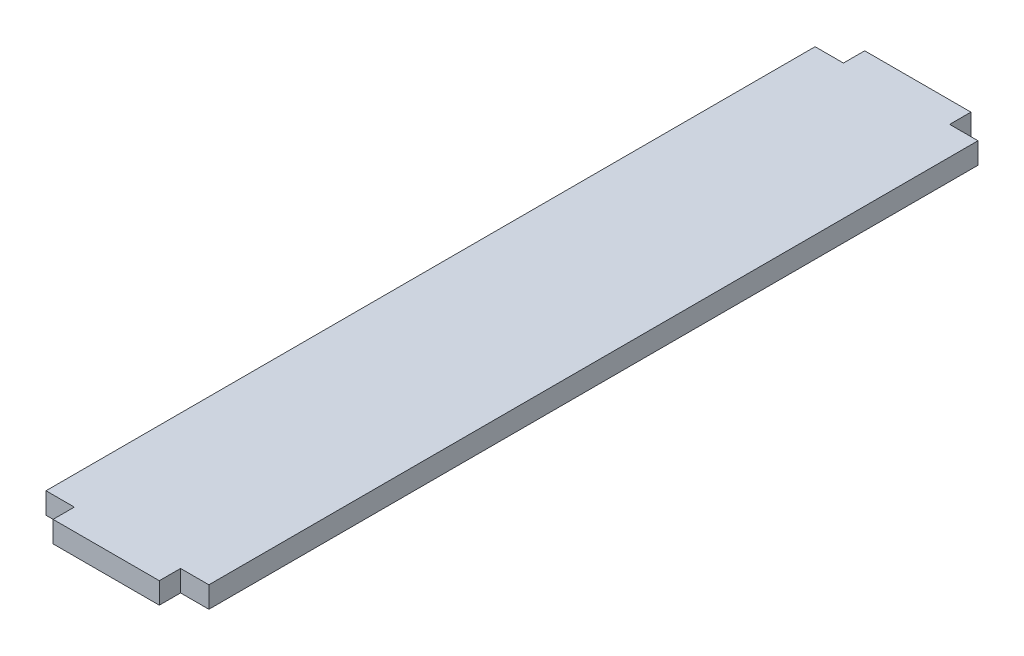
SolidWorks part; units mm, degrees
material "AISI 304"
ref_plane "Front Plane" through (0, 0, 0) normal (0, 0, 1) x (1, 0, 0)
ref_plane "Top Plane" through (0, 0, 0) normal (0, 1, 0) x (1, 0, 0)
ref_plane "Right Plane" through (0, 0, 0) normal (1, 0, 0) x (0, 0, -1)
sketch "Sketch1" plane through (0, 0, 0) normal (0, 1, 0) x (1, 0, 0)
  line L0 (3.75, 27.15) -> (5.75, 27.15)
  line L1 (-5.75, -27.15) -> (-3.75, -27.15)
  line L2 (-5.75, -27.15) -> (-5.75, -19.45)
  line L3 (-5.75, 27.15) -> (-3.75, 27.15)
  line L4 (5.75, -27.15) -> (5.75, -14.45)
  line L5 (-5.75, -27.15) -> (5.75, 27.15) construction
  line L6 (-5.75, 27.15) -> (5.75, -27.15) construction
  line L8 (3.75, 27.15) -> (3.75, 28.65)
  line L9 (3.75, 28.65) -> (-3.75, 28.65)
  line L10 (-3.75, 27.15) -> (-3.75, 28.65)
  line L12 (-3.75, -27.15) -> (-3.75, -28.65)
  line L13 (-3.75, -28.65) -> (3.75, -28.65)
  line L14 (3.75, -27.15) -> (3.75, -28.65)
  line L15 (3.75, -27.15) -> (5.75, -27.15)
  line L16 (-5.75, -17.75) -> (-5.75, 27.15)
  line L21 (5.75, -12.75) -> (5.75, 27.15)
  line L26 (-5.75, -19.45) -> (-5.75, -17.75)
  line L27 (5.75, -14.45) -> (5.75, -12.75)
  point P0 (0, 0)
  dimension "D1" = 7.5
  dimension "D2" = 2
  dimension "D3" = 2
  dimension "D4" = 1.5
  dimension "D5" = 2
  dimension "D6" = 2
  dimension "D7" = 1.5
  dimension "D8" = 54.3
extrude "Boss-Extrude1" add sketch "Sketch1" along normal blind 1.5
